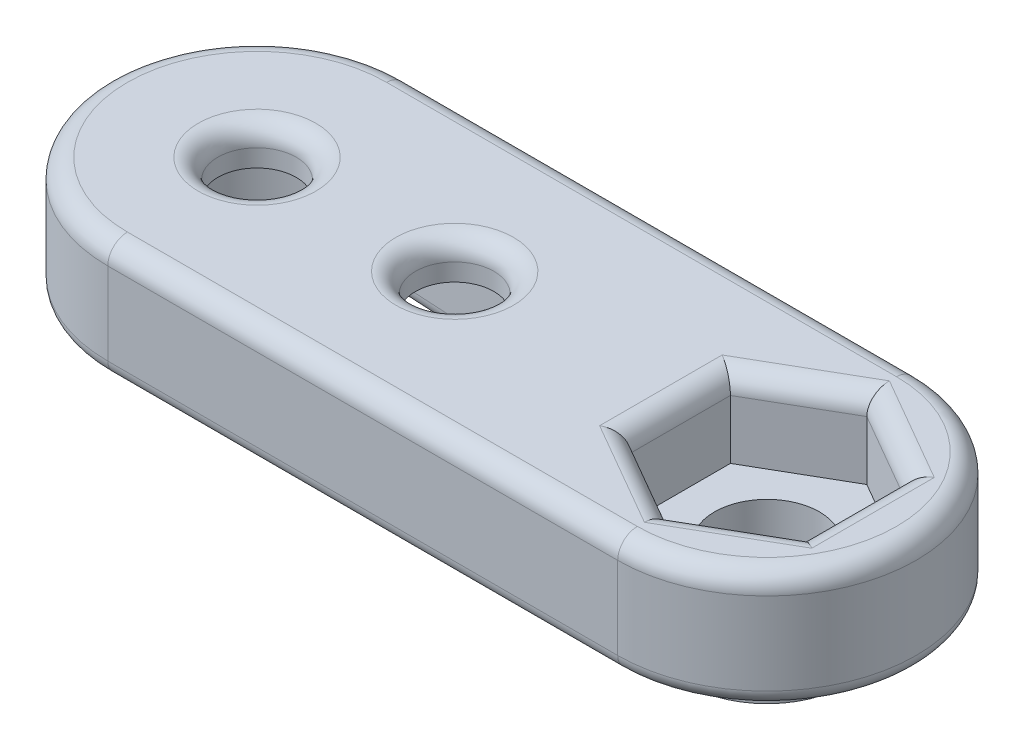
SolidWorks part; units mm, degrees
ref_plane "Front Plane" through (0, 0, 0) normal (0, 0, 1) x (1, 0, 0)
ref_plane "Top Plane" through (0, 0, 0) normal (0, 1, 0) x (1, 0, 0)
ref_plane "Right Plane" through (0, 0, 0) normal (1, 0, 0) x (0, 0, -1)
sketch "Sketch1" plane through (0, 0, 0) normal (0, 1, 0) x (1, 0, 0)
  line L0 (2.2864, 2.65) -> (14.1103, 1.997)
  line L1 (2.2864, -2.65) -> (14.1103, -1.997)
  line L2 (0, 0) -> (14, 0) construction
  line L4 (0, 6.04) -> (20.6375, 6.04)
  line L5 (24.1375, -2.0207) -> (24.1375, 2.0207)
  line L8 (0, -6.04) -> (20.6375, -6.04)
  line L9 (24.1375, 2.0207) -> (20.6375, 4.0415)
  line L10 (20.6375, 4.0415) -> (17.1375, 2.0207)
  line L11 (17.1375, 2.0207) -> (17.1375, -2.0207)
  line L12 (17.1375, -2.0207) -> (20.6375, -4.0415)
  line L13 (20.6375, -4.0415) -> (24.1375, -2.0207)
  circle A0 centre (0, 0) radius 3.5 construction
  arc A1 (14.1103, 1.997) -> (14.1103, -1.997) centre (14, 0) cw
  arc A2 (2.2864, 2.65) -> (2.2864, -2.65) centre (0, 0) ccw
  circle A3 centre (14, 0) radius 0.5 construction
  circle A4 centre (12, 0) radius 0.5 construction
  circle A5 centre (10, 0) radius 0.5 construction
  circle A6 centre (8, 0) radius 0.5 construction
  circle A7 centre (6, 0) radius 0.5 construction
  circle A8 centre (4, 0) radius 0.5 construction
  arc A12 (0, -6.04) -> (0, 6.04) centre (0, 0) cw
  circle A17 centre (20.6375, 0) radius 4.064 construction
  arc A18 (20.6375, -6.04) -> (20.6375, 6.04) centre (20.6375, 0) ccw
  circle A19 centre (20.6375, 0) radius 3.5 construction
  point P4 (16, 0)
  point P6 (-3.5, 0)
  dimension "D1" = 7
  dimension "D5" = 1
  dimension "D8" = 2.54
  dimension "D10" = 20.6375
  dimension "D4" = 2
  dimension "D9" = 8.128
  dimension "D2" = 19.5
  dimension "D3" = 5.3
  dimension "D7" = 2
  dimension "D11" = 7
  dimension "D6" = 6
extrude "Boss-Extrude1" add sketch "Sketch1" along normal blind 4.5
sketch "Sketch2" plane through (0, 4.5, 0) normal (0, 1, 0) x (1, 0, 0)
  line L0 (0, 0) -> (16, 0) construction
  line L1 (24.1375, 2.0207) -> (20.6375, 4.0415) construction
  line L2 (20.6375, 4.0415) -> (17.1375, 2.0207) construction
  line L3 (17.1375, 2.0207) -> (17.1375, -2.0207) construction
  line L4 (20.6375, 6.04) -> (0, 6.04)
  line L5 (0, -6.04) -> (20.6375, -6.04)
  line L6 (17.1375, -2.0207) -> (20.6375, -4.0415) construction
  line L7 (20.6375, -4.0415) -> (24.1375, -2.0207) construction
  line L8 (20.6375, 6.04) -> (0, 6.04)
  line L9 (0, -6.04) -> (20.6375, -6.04)
  line L10 (24.1375, -2.0207) -> (24.1375, 2.0207) construction
  line L11 (24.1375, 2.0207) -> (20.6375, 4.0415)
  line L12 (20.6375, 4.0415) -> (17.1375, 2.0207)
  line L13 (17.1375, 2.0207) -> (17.1375, -2.0207)
  line L14 (17.1375, -2.0207) -> (20.6375, -4.0415)
  line L15 (20.6375, -4.0415) -> (24.1375, -2.0207)
  line L16 (24.1375, -2.0207) -> (24.1375, 2.0207)
  circle A0 centre (0, 0) radius 1.5875
  circle A1 centre (8, 0) radius 1.5875
  arc A2 (14.1103, -1.997) -> (14.1103, 1.997) centre (14, 0) ccw construction
  arc A5 (20.6375, -6.04) -> (20.6375, 6.04) centre (20.6375, 0) ccw
  arc A6 (20.6375, -6.04) -> (20.6375, 6.04) centre (20.6375, 0) ccw
  arc A9 (0, 6.04) -> (0, -6.04) centre (0, 0) ccw
  arc A17 (0, 6.04) -> (0, -6.04) centre (0, 0) ccw
  point P15 (8, 0)
  dimension "D2" = 3.175
  dimension "D3" = 3.175
  dimension "D1" = 0
extrude "Boss-Extrude2" add sketch "Sketch2" along normal offset from surface (1.5 mm away) 6 up to face at (10.3187, 0, 0)
sketch "Sketch3" plane through (0, 0, 0) normal (0, -1, 0) x (1, 0, 0)
  line L6 (20.6375, 6.04) -> (0, 6.04)
  line L7 (0, -6.04) -> (20.6375, -6.04)
  line L10 (20.6375, 6.04) -> (0, 6.04)
  line L11 (0, -6.04) -> (20.6375, -6.04)
  arc A2 (20.6375, -6.04) -> (20.6375, 6.04) centre (20.6375, 0) ccw
  arc A3 (20.6375, -6.04) -> (20.6375, 6.04) centre (20.6375, 0) ccw
  arc A11 (0, 6.04) -> (0, -6.04) centre (0, 0) ccw
  arc A17 (0, 6.04) -> (0, -6.04) centre (0, 0) ccw
  dimension "D1" = 0
extrude "Cut-Extrude1" cut sketch "Sketch3" against normal offset from surface (1.2375 mm away) 4.7625 up to face at (8, 6, -1.5875)
sketch "Sketch5" plane through (0, 1.2375, 0) normal (0, 1, 0) x (1, 0, 0)
  line L0 (20.6375, 4.0415) -> (24.1375, 2.0207) construction
  line L1 (17.1375, 2.0207) -> (20.6375, 4.0415) construction
  line L2 (17.1375, -2.0207) -> (17.1375, 2.0207) construction
  line L3 (20.6375, -4.0415) -> (17.1375, -2.0207) construction
  line L4 (24.1375, -2.0207) -> (20.6375, -4.0415) construction
  line L5 (24.1375, 2.0207) -> (24.1375, -2.0207) construction
  line L6 (20.6375, 4.0415) -> (24.1375, 2.0207)
  line L7 (17.1375, 2.0207) -> (20.6375, 4.0415)
  line L8 (17.1375, -2.0207) -> (17.1375, 2.0207)
  line L9 (20.6375, -4.0415) -> (17.1375, -2.0207)
  line L10 (24.1375, -2.0207) -> (20.6375, -4.0415)
  line L11 (24.1375, 2.0207) -> (24.1375, -2.0207)
  line L12 (17.1375, 2.0207) -> (24.1375, -2.0207) construction
  circle A0 centre (20.6375, 0) radius 2.125
  point P5 (20.6375, 0)
  dimension "D1" = 4.25
extrude "Boss-Extrude4" add sketch "Sketch5" along normal blind 1.5875
sketch "Sketch4" plane through (0, 6, 0) normal (0, 1, 0) x (1, 0, 0)
  circle A0 centre (20.6375, 0) radius 3.25
  circle A1 centre (20.6375, 0) radius 2.125
  circle A3 centre (20.6375, 0) radius 2.125 construction
  dimension "D1" = 6.5
extrude "Boss-Extrude3" add sketch "Sketch4" against normal blind 1.778 from surface starting at face at (7.2242, 1.2375, 0)
fillet "Fillet2" radius 0.635 9 edges at (10.3187, 1.2375, -6.04) (-6.04, 1.2375, 0) (10.3187, 1.2375, 6.04) (-3.5, 1.2375, 0) (8.1983, 1.2375, -2.3235) (16, 1.2375, 0) (8.1983, 1.2375, 2.3235) (26.6775, 1.2375, 0) (20.6375, 1.2375, -3.25)
fillet "Fillet3" radius 0.7937 12 edges at (10.3187, 6, 6.04) (-6.04, 6, 0) (10.3187, 6, -6.04) (0, 6, -1.5875) (8, 6, -1.5875) (26.6775, 6, 0) (22.3875, 6, -3.0311) (18.8875, 6, -3.0311) (17.1375, 6, 0) (18.8875, 6, 3.0311) (22.3875, 6, 3.0311) (24.1375, 6, 0)
